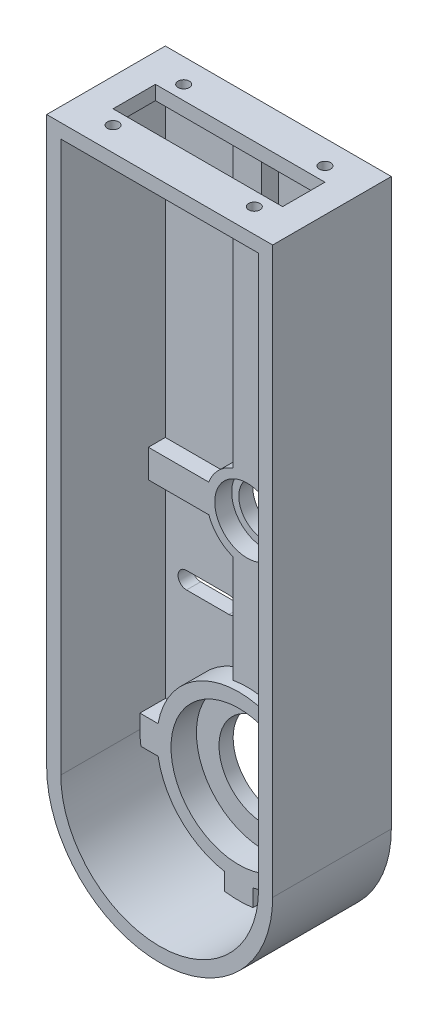
SolidWorks part; units mm, degrees
ref_plane "Plano frontal" through (0, 0, 0) normal (0, 0, 1) x (1, 0, 0)
ref_plane "Plano superior" through (0, 0, 0) normal (0, 1, 0) x (1, 0, 0)
ref_plane "Plano direito" through (0, 0, 0) normal (1, 0, 0) x (0, 0, -1)
sketch "Esboço1" plane through (0, 0, 0) normal (0, 0, 1) x (1, 0, 0)
  line L1 (-40, -100) -> (40, -100) construction
  line L2 (-40, -100) -> (-40, 100)
  line L3 (-40, 100) -> (40, 100)
  line L4 (40, -100) -> (40, 100)
  line L5 (-40, -100) -> (40, 100) construction
  line L6 (-40, 100) -> (40, -100) construction
  arc A0 (-40, -100) -> (40, -100) centre (0, -100) ccw
  circle A1 centre (0, -100) radius 16
  point P0 (0, 0)
  dimension "D3" = 32
  dimension "D1" = 80
  dimension "D2" = 200
extrude "Ressalto-extrusão1" add sketch "Esboço1" along normal blind 42
shell "Casca1" thickness 5 removed face at (0, -10, 42) removed face at (16, -100, 42)
sketch "Esboço3" plane through (0, 100, 0) normal (0, 1, 0) x (1, 0, 0)
  line L0 (0, -42) -> (0, 0) construction
  line L1 (40, -42) -> (-40, -42) construction
  line L2 (40, 0) -> (-40, 0) construction
  line L3 (40, -21) -> (-40, -21) construction
  line L4 (40, -42) -> (40, 0) construction
  line L5 (-40, -42) -> (-40, 0) construction
  line L7 (30, -13.5) -> (-30, -13.5)
  line L8 (30, -13.5) -> (30, -28.5)
  line L9 (30, -28.5) -> (-30, -28.5)
  line L10 (-30, -13.5) -> (-30, -28.5)
  line L11 (30, -13.5) -> (-30, -28.5) construction
  line L12 (30, -28.5) -> (-30, -13.5) construction
  line L13 (25, -8.5) -> (-25, -8.5) construction
  line L14 (25, -8.5) -> (25, -33.5) construction
  line L15 (25, -33.5) -> (-25, -33.5) construction
  line L16 (-25, -8.5) -> (-25, -33.5) construction
  line L17 (25, -8.5) -> (-25, -33.5) construction
  line L18 (25, -33.5) -> (-25, -8.5) construction
  circle A0 centre (25, -33.5) radius 2
  circle A1 centre (-25, -33.5) radius 2
  circle A2 centre (-25, -8.5) radius 2
  circle A3 centre (25, -8.5) radius 2
  point P12 (0, -21)
  point P17 (0, -21)
  dimension "D5" = 4
  dimension "D1" = 60
  dimension "D2" = 15
  dimension "D3" = 50
  dimension "D4" = 25
extrude "Corte-extrusão1" cut sketch "Esboço3" against normal up to surface (5 mm away) up to face at (0, 95, 23.5)
sketch "Esboço4" plane through (0, 0, 5) normal (0, 0, 1) x (1, 0, 0)
  circle A0 centre (0, -100) radius 24
  circle A1 centre (0, -100) radius 29
  dimension "D1" = 48
  dimension "D2" = 58
extrude "Ressalto-extrusão2" add sketch "Esboço4" along normal blind 9
sketch "Esboço5" plane through (0, 0, 5) normal (0, 0, 1) x (1, 0, 0)
  circle A0 centre (0, -20) radius 9
  circle A1 centre (0, -100) radius 16 construction
  dimension "D1" = 80
  dimension "D2" = 18
extrude "Corte-extrusão2" cut sketch "Esboço5" against normal up to surface (5 mm away) up to face at (0, -10, 0)
sketch "Esboço6" plane through (0, 0, 5) normal (0, 0, 1) x (1, 0, 0)
  circle A0 centre (0, -20) radius 11.5
  circle A1 centre (0, -20) radius 14.5
  dimension "D1" = 23
  dimension "D2" = 29
extrude "Ressalto-extrusão3" add sketch "Esboço6" along normal blind 6
sketch "Esboço7" plane through (0, 0, 14) normal (0, 0, 1) x (1, 0, 0)
  line L0 (29, -100) -> (35, -100)
  line L1 (-29, -100) -> (-35, -100)
  line L2 (0, -129) -> (0, -135)
  circle A0 centre (0, -100) radius 29 construction
  circle A1 centre (0, -100) radius 29 construction
  arc A2 (-35, -100) -> (35, -100) centre (0, -100) ccw construction
rib "Nervura1" sketch "Esboço7" sketch "Esboço7" thickness 10 extrusion direction normal to sketch draft on no parameters "D1"=10
sketch "Esboço8" plane through (0, 0, 11) normal (0, 0, 1) x (1, 0, 0)
  line L0 (14.5, -20) -> (35, -20)
  line L1 (35, -95) -> (35, 95) construction
  line L2 (-14.5, -20) -> (-35, -20)
  line L3 (-35, 95) -> (-35, -100) construction
  line L4 (0, -5.5) -> (0, 95)
  line L5 (35, 95) -> (-35, 95) construction
  line L6 (0, -34.5) -> (0, -71)
  circle A0 centre (0, -20) radius 14.5 construction
  circle A1 centre (0, -20) radius 14.5 construction
  arc A2 (28.5657, -95) -> (-28.5657, -95) centre (0, -100) ccw construction
rib "Nervura2" sketch "Esboço8" sketch "Esboço8" thickness 10 extrusion direction normal to sketch draft on no parameters "D1"=10
sketch "Esboço9" plane through (0, 0, 5) normal (0, 0, 1) x (1, 0, 0)
  line L0 (-27.5, -55) -> (-12.5, -55) construction
  line L1 (-27.5, -52) -> (-12.5, -52)
  line L2 (-27.5, -58) -> (-12.5, -58)
  line L3 (-40, 100) -> (-40, -100) construction
  line L4 (0, -100) -> (0, -84) construction
  arc A0 (-27.5, -52) -> (-27.5, -58) centre (-27.5, -55) ccw
  arc A1 (-12.5, -58) -> (-12.5, -52) centre (-12.5, -55) ccw
  circle A2 centre (0, -100) radius 16 construction
  point P2 (-20, -55)
  dimension "D2" = 3
  dimension "D1" = 20
  dimension "D3" = 15
  dimension "D4" = 45
extrude "Corte-extrusão3" cut sketch "Esboço9" against normal up to surface (5 mm away) up to face at (16, -100, 0)
sketch "Esboço10" plane through (0, 0, 5) normal (0, 0, 1) x (1, 0, 0)
  line L0 (0, -100) -> (35, -45.2277) construction
  line L2 (35, -95) -> (35, -25) construction
  line L3 (0, -100) -> (35, -51.266) construction
  line L7 (14.6835, -56.3488) -> (22.2163, -49.7717)
  line L8 (21.5385, -66.294) -> (28.6945, -60.0457) construction
  line L9 (22.2163, -49.7717) -> (19.5854, -46.7586)
  line L10 (19.5854, -46.7586) -> (12.0527, -53.3357)
  line L11 (12.0527, -53.3357) -> (14.6835, -56.3488)
  circle A0 centre (21.5385, -66.294) radius 1.2
  circle A1 centre (28.6945, -60.0457) radius 1.2
  dimension "D1" = 9.5
  dimension "D2" = 2.4
  dimension "D3" = 40
  dimension "D4" = 65
  dimension "D5" = 60
  dimension "D6" = 10
  dimension "D7" = 12
  dimension "D8" = 4
extrude "Corte-extrusão4" cut sketch "Esboço10" against normal up to surface (5 mm away) up to face at (-20, -55, 0)
ref_plane "Plano1" through (0, -65, 0) normal (0, -1, 0) x (-1, 0, 0)
sketch "Esboço11" plane through (0, -65, 0) normal (0, -1, 0) x (-1, 0, 0)
  line L0 (-40, -21) -> (-31, -21)
  line L1 (-40, -42) -> (-40, 0) construction
  line L2 (-31, -21) -> (-31, -36)
  line L3 (-31, -36) -> (-33, -36)
  line L4 (-33, -36) -> (-33, -26)
  line L5 (-33, -26) -> (-40, -26)
  line L6 (-40, -26) -> (-40, -21)
  dimension "D1" = 9
  dimension "D2" = 7
  dimension "D3" = 15
  dimension "D4" = 10
extrude "Ressalto-extrusão4" add sketch "Esboço11" along normal blind 4
fillet "Filete1" radius 1.5 3 edges at (31, -67, 21) (31, -67, 36) (33, -67, 36)
pattern_linear "Padrão linear1" count 3 spacing 65 along (0, 1, 0) of "Filete1", "Ressalto-extrusão4"
